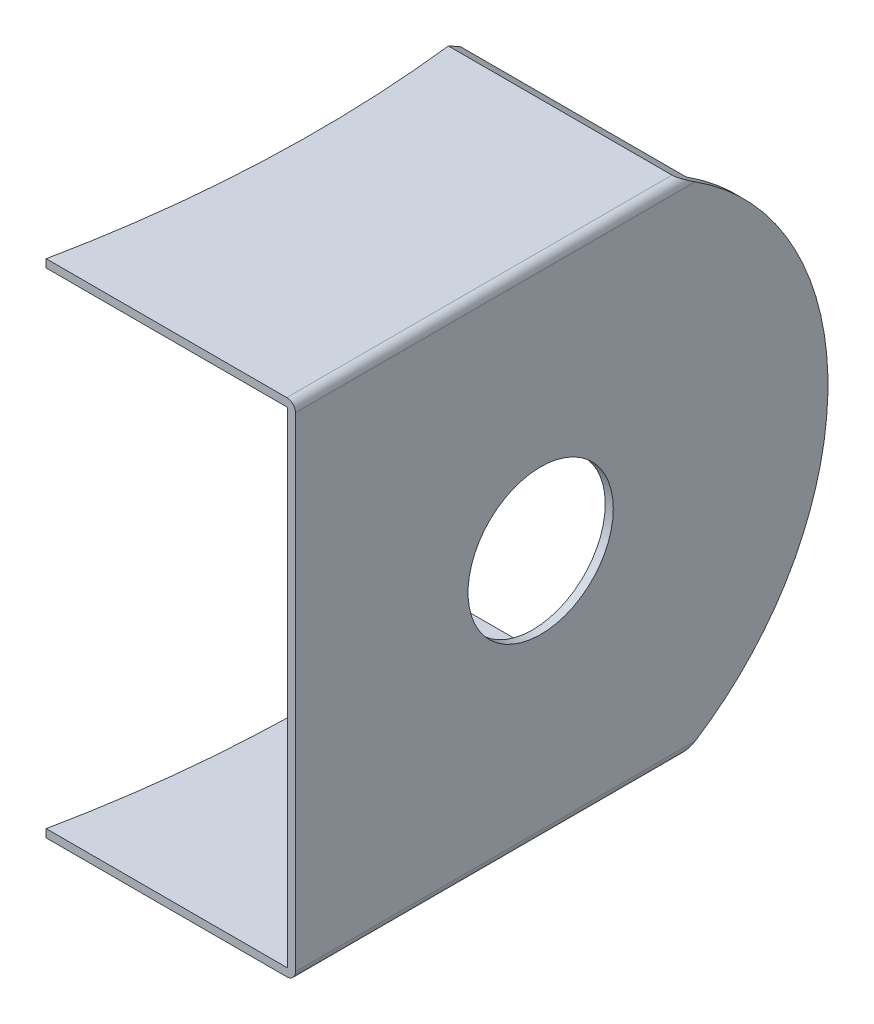
SolidWorks part; units mm, degrees
note: The reader was unsure of these and kept them because the rebuilt part matched: flange length of "Edge-Flange1".
material "Galvanized Steel"
ref_plane "Front Plane" through (0, 0, 0) normal (0, 0, 1) x (1, 0, 0)
ref_plane "Top Plane" through (0, 0, 0) normal (0, 1, 0) x (1, 0, 0)
ref_plane "Right Plane" through (0, 0, 0) normal (1, 0, 0) x (0, 0, -1)
sketch "Sketch1" plane through (0, 0, 0) normal (1, 0, 0) x (0, 0, -1)
  line L1 (-365, -75) -> (365, -75)
  line L2 (-365, -75) -> (-365, 75)
  line L3 (-365, 75) -> (365, 75)
  line L4 (365, -75) -> (365, 75)
  line L5 (-365, -75) -> (365, 75) construction
  line L6 (-365, 75) -> (365, -75) construction
  point P0 (0, 0)
  dimension "D1" = 150
  dimension "D2" = 730
base flange "Base-Flange1" sketch "Sketch1" thickness 2.5 reverse thickness direction no parameters "D1"=0.2
edge flange "Edge-Flange1" sketch "Sketch10" flange profiles "Sketch10", "Sketch11" flange angle 90 flange length 130 flange position bend outside bend radius 0.2 thickness 2.5 relief rectangular parameters "D6"=10, "D8"=1
sketch "Sketch10" plane through (-2.5, 75, 0) normal (0, -1, 0) x (0, 0, 1)
  line L2 (-365, 0) -> (-365, 127.5)
  line L3 (-365, 127.5) -> (365, 127.5)
  line L4 (365, 127.5) -> (365, 0)
  line L5 (365, 0) -> (-365, 0) construction
  line L6 (365, 0) -> (-365, 0)
sketch "Sketch11" plane through (-2.5, -75, 0) normal (0, 1, 0) x (0, 0, -1)
  line L0 (365, 0) -> (-365, 0) construction
  line L1 (365, 0) -> (-365, 0)
  line L2 (365, 0) -> (365, 127.5)
  line L3 (365, 127.5) -> (-365, 127.5)
  line L4 (-365, 127.5) -> (-365, 0)
bend "EdgeBend1" bend radius 0.2 bend angle 90 parameters "D5"=1
bend "EdgeBend2" bend radius 0.2 bend angle 90 parameters "D5"=2
sketch "Sketch12" plane through (0, 77.7, 0) normal (0, 1, 0) x (1, 0, 0)
sketch "Sketch13" plane through (0, 0, 0) normal (1, 0, 0) x (0, 0, -1)
  line L0 (365, -75) -> (365, 75) construction
  line L1 (-365, 75) -> (-365, -75) construction
  circle A0 centre (265, 0) radius 22.5
  circle A1 centre (-290, 0) radius 22.5
  dimension "D1" = 45
  dimension "D2" = 100
  dimension "D3" = 45
  dimension "D4" = 75
extrude "Cut-Extrude2" cut sketch "Sketch13" against normal blind 10
sketch "Sketch14" plane through (0, 0, 0) normal (1, 0, 0) x (0, 0, -1)
  line L1 (189.0395, 122.5591) -> (-442.2981, 122.5591)
  line L2 (189.0395, 122.5591) -> (189.0395, -150.5984)
  line L3 (189.0395, -150.5984) -> (-442.2981, -150.5984)
  line L4 (-442.2981, 122.5591) -> (-442.2981, -150.5984)
extrude "Cut-Extrude3" cut sketch "Sketch14" against normal through all both and the other way through all
sketch "Sketch15" plane through (0, 0, 0) normal (1, 0, 0) x (0, 0, -1)
  line L0 (302.2666, 80.8221) -> (310.532, 105.3518)
  line L1 (310.532, 105.3518) -> (400.6684, 94.5662)
  line L2 (400.6684, 94.5662) -> (380.2529, -108.0482)
  line L3 (380.2529, -108.0482) -> (291.2869, -85.0294)
  arc A0 (291.2869, -85.0294) -> (302.2666, 80.8221) centre (265, 0) ccw
  dimension "D1" = 178
extrude "Cut-Extrude4" cut sketch "Sketch15" against normal through all both and the other way through all
sketch "Sketch17" plane through (0, 77.7, 0) normal (0, 1, 0) x (1, 0, 0)
  line L3 (-169.943, 157.4369) -> (-165.6584, 335.0088)
  line L5 (-165.6584, 335.0088) -> (-74.3157, 325.1467)
  line L7 (-169.943, 157.4369) -> (-78.7815, 181.8302)
  circle A0 centre (-445.9804, 265) radius 376.5 construction
  arc A1 (-78.7815, 181.8302) -> (-74.3157, 325.1467) centre (-445.9804, 265) ccw
  dimension "D1" = 376.5
  dimension "D2" = 177.5719
extrude "Cut-Extrude5" cut sketch "Sketch17" against normal through all normal cut yes
sketch "Bend-Lines1" [suppressed] plane through (0, 0, 0) normal (0, 1, 0) x (1, 0, 0)
sketch "Bounding-Box1" [suppressed] plane through (0, 0, 0) normal (0, 1, 0) x (1, 0, 0)
sheet metal parameters "Sheet-Metal1" thickness 2.5 parameters "D1"=0.2
flat pattern "Flat-Pattern1" [suppressed]
sketch "Bend-Lines2" plane through (0, 0, 0) normal (0, 1, 0) x (1, 0, 0)
sketch3d "Bounding-Box2" [suppressed]
  line L0 (-227, -60, 0) -> (227, -60, 0) construction
  line L1 (-227, 60, 0) -> (227, 60, 0) construction
  line L2 (-227, -60, 0) -> (-227, 60, 0) construction
  line L3 (227, -60, 0) -> (227, 60, 0) construction
sheet metal parameters "Sheet-Metal2" thickness 2.5 parameters "D1"=0.2
flat pattern "Flat-Pattern1"
sketch "Bend-Lines2" plane through (0, 0, 0) normal (1, 0, 0) x (0, 0, -1)
  line L0 (-227, -61.1388) -> (227, -61.1388) construction
  line L1 (227, 61.1388) -> (-227, 61.1388) construction
  line L2 (-227, -61.1388) -> (227, -61.1388) construction
  line L3 (227, 61.1388) -> (-227, 61.1388) construction
sketch3d "Bounding-Box2" [suppressed]
  line L0 (227, -139.5777, 0) -> (-227, -139.5777, 0) construction
  line L1 (227, 139.5777, 0) -> (-227, 139.5777, 0) construction
  line L2 (227, -139.5777, 0) -> (227, 139.5777, 0) construction
  line L3 (-227, -139.5777, 0) -> (-227, 139.5777, 0) construction
bend of the flat pattern "Flatten-<EdgeBend1>1"
bend of the flat pattern "Flatten-<EdgeBend2>1"
sheet metal parameters "Sheet-Metal4" thickness 2.5 parameters "D1"=0.2
flat pattern "Flat-Pattern1"
sketch "Bend-Lines2" plane through (0, 0, 0) normal (1, 0, 0) x (0, 0, -1)
  line L0 (-340, -61.1388) -> (340, -61.1388) construction
  line L1 (340, 61.1388) -> (-340, 61.1388) construction
  line L2 (-340, -61.1388) -> (340, -61.1388) construction
  line L3 (340, 61.1388) -> (-340, 61.1388) construction
sketch3d "Bounding-Box2" [suppressed]
  line L0 (340, -177.6863, 0) -> (-340, -177.6863, 0) construction
  line L1 (340, 177.6863, 0) -> (-340, 177.6863, 0) construction
  line L2 (340, -177.6863, 0) -> (340, 177.6863, 0) construction
  line L3 (-340, -177.6863, 0) -> (-340, 177.6863, 0) construction
bend of the flat pattern "Flatten-<EdgeBend1>1"
bend of the flat pattern "Flatten-<EdgeBend2>1"
sheet metal parameters "Sheet-Metal7" thickness 2.5 parameters "D1"=0.2
flat pattern "Flat-Pattern1"
sketch "Bend-Lines2" plane through (0, 0, 0) normal (1, 0, 0) x (0, 0, -1)
  line L0 (189.0395, -76.1388) -> (365, -76.1388) construction
  line L1 (365, 76.1388) -> (189.0395, 76.1388) construction
  line L2 (189.0395, -76.1388) -> (365, -76.1388) construction
  line L3 (365, 76.1388) -> (189.0395, 76.1388) construction
sketch3d "Bounding-Box2" [suppressed]
  line L0 (189.0395, 204.5777, 0) -> (189.0395, -204.5777, 0) construction
  line L1 (365, 204.5777, 0) -> (365, -204.5777, 0) construction
  line L2 (189.0395, 204.5777, 0) -> (365, 204.5777, 0) construction
  line L3 (189.0395, -204.5777, 0) -> (365, -204.5777, 0) construction
bend of the flat pattern "Flatten-<EdgeBend1>1"
bend of the flat pattern "Flatten-<EdgeBend2>1"
sheet metal parameters "Sheet-Metal8" thickness 2.5 parameters "D1"=0.2
flat pattern "Flat-Pattern1" [suppressed]
sketch "Bend-Lines2" plane through (0, 0, 0) normal (1, 0, 0) x (0, 0, -1)
  line L0 (312.7593, -76.1388) -> (189.0395, -76.1388) construction
  line L1 (308.559, 76.1388) -> (189.0395, 76.1388) construction
  line L2 (312.7593, -76.1388) -> (189.0395, -76.1388) construction
  line L3 (308.559, 76.1388) -> (189.0395, 76.1388) construction
sketch3d "Bounding-Box2" [suppressed]
  line L0 (189.0395, -204.5777, 0) -> (189.0395, 204.5777, 0) construction
  line L1 (354, -204.5777, 0) -> (354, 204.5777, 0) construction
  line L2 (189.0395, -204.5777, 0) -> (354, -204.5777, 0) construction
  line L3 (189.0395, 204.5777, 0) -> (354, 204.5777, 0) construction
bend of the flat pattern "Flatten-<EdgeBend1>1"
bend of the flat pattern "Flatten-<EdgeBend2>1"
sketch "Sketch12-1" [suppressed] plane through (0, 74.5777, 0) normal (1, 0, 0) x (0, -1, 0)
sheet metal parameters "Sheet-Metal11" thickness 2.5 parameters "D1"=0.2
flat pattern "Flat-Pattern1" [suppressed]
sketch "Bend-Lines2" plane through (0, 0, 0) normal (1, 0, 0) x (0, 0, -1)
  line L0 (312.7593, -76.1388) -> (189.0395, -76.1388) construction
  line L1 (308.559, 76.1388) -> (189.0395, 76.1388) construction
  line L2 (312.7593, -76.1388) -> (189.0395, -76.1388) construction
  line L3 (308.559, 76.1388) -> (189.0395, 76.1388) construction
sketch3d "Bounding-Box2" [suppressed]
  line L0 (189.0395, 151.8003, 0) -> (189.0395, -151.8003, 0) construction
  line L1 (354, 151.8003, 0) -> (354, -151.8003, 0) construction
  line L2 (189.0395, 151.8003, 0) -> (354, 151.8003, 0) construction
  line L3 (189.0395, -151.8003, 0) -> (354, -151.8003, 0) construction
bend of the flat pattern "Flatten-<EdgeBend1>1"
bend of the flat pattern "Flatten-<EdgeBend2>1"
sketch "Sketch12-1" plane through (0, 74.5777, 0) normal (1, 0, 0) x (0, -1, 0)
